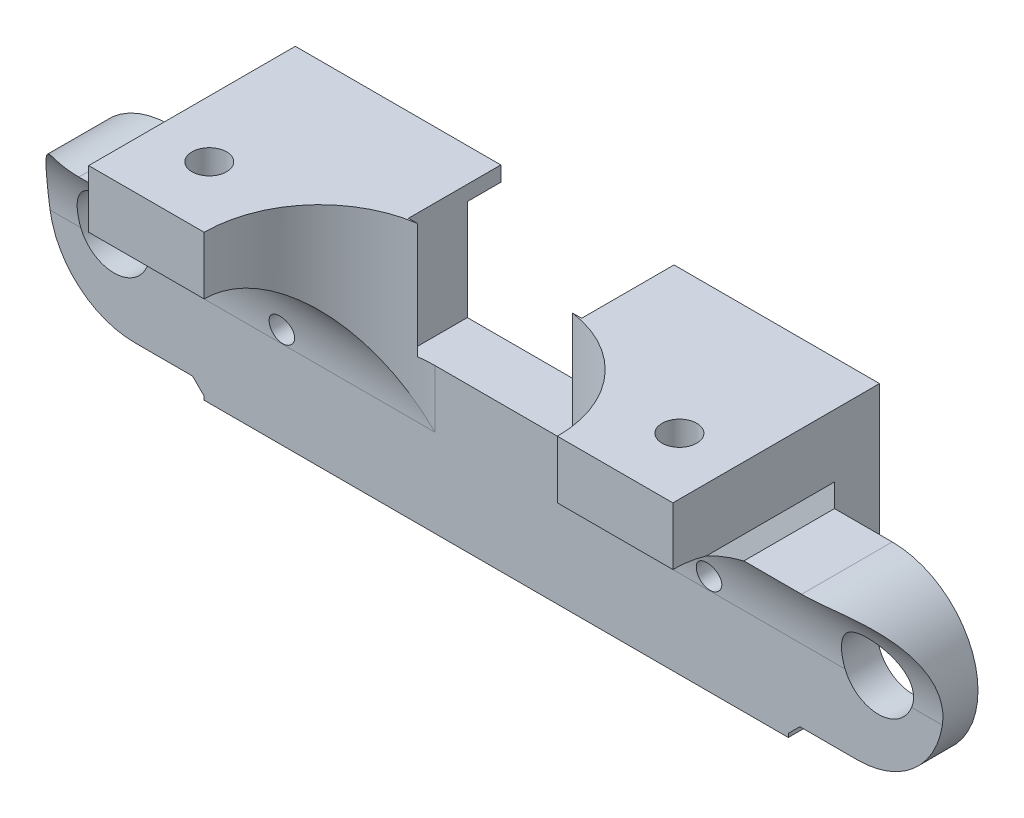
SolidWorks part; units mm, degrees
ref_plane "Front Plane" through (0, 0, 0) normal (0, 0, 1) x (1, 0, 0)
ref_plane "Top Plane" through (0, 0, 0) normal (0, 1, 0) x (1, 0, 0)
ref_plane "Right Plane" through (0, 0, 0) normal (1, 0, 0) x (0, 0, -1)
sketch "Sketch1" plane through (0, 0, 0) normal (0, 0, 1) x (1, 0, 0)
  line L12 (24, 12.55) -> (6.08, 12.55)
  line L13 (6.08, 12.55) -> (-6.08, 12.55)
  line L14 (-6.08, 12.55) -> (-24, 12.55)
  line L15 (-24, 12.55) -> (-24, -7.45)
  line L16 (-24, -7.45) -> (24, -7.45)
  line L17 (24, -7.45) -> (24, 12.55)
  line L18 (24, 12.55) -> (6.08, 12.55)
  line L19 (6.08, 12.55) -> (-6.08, 12.55)
  line L20 (-6.08, 12.55) -> (-24, 12.55)
  line L21 (-24, 12.55) -> (-24, -7.45)
  line L22 (-24, -7.45) -> (24, -7.45)
  line L23 (24, -7.45) -> (24, 12.55)
  dimension "D1" = 0
extrude "Boss-Extrude1" add sketch "Sketch1" along normal blind 5
sketch "Sketch2" plane through (0, 0, 5) normal (0, 0, 1) x (1, 0, 0)
  line L4 (25.3, -8.75) -> (25.3, 13.85)
  line L5 (25.3, 13.85) -> (-25.3, 13.85)
  line L6 (-25.3, 13.85) -> (-25.3, -8.75)
  line L7 (-25.3, -8.75) -> (25.3, -8.75)
  line L8 (24, -7.45) -> (24, 12.55)
  line L9 (24, 12.55) -> (-24, 12.55)
  line L10 (-24, 12.55) -> (-24, -7.45)
  line L11 (-24, -7.45) -> (24, -7.45)
  line L12 (24, -7.45) -> (24, 12.55)
  line L13 (24, 12.55) -> (-24, 12.55)
  line L14 (-24, 12.55) -> (-24, -7.45)
  line L15 (-24, -7.45) -> (24, -7.45)
  dimension "D1" = 0
  dimension "D2" = 1.3
extrude "Boss-Extrude2" add sketch "Sketch2" against normal offset from surface (7.9 mm away) 0.1
sketch "Sketch3" plane through (0, 0, 0) normal (0, 0, -1) x (-1, 0, 0)
  circle A0 centre (-18.5, 0) radius 1.1
  circle A1 centre (18.5, 0) radius 1.1
  dimension "D1" = 2.2
  dimension "D2" = 2.2
extrude "Cut-Extrude1" cut sketch "Sketch3" along normal through all both and the other way through all
sketch "Sketch4" plane through (0, 0, 5) normal (0, 0, 1) x (1, 0, 0)
  line L0 (25.3, -7.4396) -> (31.3, -7.4396)
  line L1 (25.3, 13.85) -> (25.3, -8.75) construction
  line L2 (0, -1008.75) -> (0, 48991.25) construction
  line L3 (31.3, 7.4204) -> (25.3, 7.4204)
  line L4 (25.3, 7.4204) -> (25.3, -7.4396)
  line L5 (25.3, -8.75) -> (-25.3, -8.75) construction
  line L6 (-25.3, -7.4396) -> (-31.3, -7.4396)
  line L7 (-25.3, 7.4204) -> (-25.3, -7.4396)
  line L8 (-31.3, 7.4204) -> (-25.3, 7.4204)
  arc A0 (31.3, -7.4396) -> (31.3, 7.4204) centre (31.3, -0.0096) ccw
  arc A1 (-31.3, -7.4396) -> (-31.3, 7.4204) centre (-31.3, -0.0096) cw
  point P15 (0, -8.75)
  dimension "D1" = 6
  dimension "D2" = 1.3104
  dimension "D3" = 14.86
extrude "Boss-Extrude3" add sketch "Sketch4" against normal blind 3
chamfer "Chamfer1" distance 1 angle 45 6 edges at (25.3, 7.4204, 3.5) (25.3, -0.0096, 2) (25.3, -7.4396, 3.5) (-25.3, 7.4204, 3.5) (-25.3, -0.0096, 2) (-25.3, -7.4396, 3.5)
sketch "Sketch5" plane through (0, 0, 2) normal (0, 0, -1) x (-1, 0, 0)
  line L0 (-968.7, -0.0096) -> (49031.3, -0.0096) construction
  line L2 (0, -1008.75) -> (0, 48991.25) construction
  line L3 (-25.3, -8.75) -> (25.3, -8.75) construction
  circle A2 centre (-33.1, -0.0096) radius 3.1
  circle A3 centre (33.1, -0.0096) radius 3.1
  point P0 (31.3, -0.0096)
  point P15 (0, -8.75)
  dimension "D1" = 6.2
  dimension "D2" = 1.8
extrude "Cut-Extrude2" cut sketch "Sketch5" against normal blind 3
sketch "Sketch6" plane through (0, 0, 5) normal (0, 0, 1) x (1, 0, 0)
  line L0 (25.3, 13.85) -> (-25.3, 13.85) construction
  line L1 (-25.3, 13.85) -> (-15.3, 13.85)
  line L2 (-25.3, 13.85) -> (-25.3, 8.85)
  line L3 (-25.3, 8.85) -> (-15.3, 8.85)
  line L4 (-15.3, 13.85) -> (-15.3, 8.85)
  line L5 (-25.3, 13.85) -> (-25.3, 8.4204) construction
  line L6 (0, 21.1699) -> (0, -25.8518) construction
  line L7 (25.3, 8.85) -> (15.3, 8.85)
  line L8 (15.3, 13.85) -> (15.3, 8.85)
  line L9 (25.3, 13.85) -> (15.3, 13.85)
  line L10 (25.3, 13.85) -> (25.3, 8.85)
  dimension "D1" = 5
  dimension "D2" = 10
extrude "Boss-Extrude4" add sketch "Sketch6" along normal blind 10
fillet "Fillet1" radius 10 4 edges at (15.3, 11.35, 5) (-15.3, 11.35, 5) (-20.3, 8.85, 5) (20.3, 8.85, 5)
sketch "Sketch7" plane through (0, 13.85, 0) normal (0, 1, 0) x (1, 0, 0)
  line L0 (0, 12.6059) -> (0, -14.8059) construction
  line L1 (-25.3, 2.9) -> (25.3, 2.9) construction
  line L2 (7.5, -5.1) -> (-7.5, -5.1)
  line L3 (7.5, -5.1) -> (7.5, 2.9)
  line L4 (7.5, 2.9) -> (-7.5, 2.9)
  line L5 (-7.5, -5.1) -> (-7.5, 2.9)
  line L6 (7.5, -5.1) -> (-7.5, 2.9) construction
  line L7 (7.5, 2.9) -> (-7.5, -5.1) construction
  point P3 (0, -1.1)
  dimension "D1" = 8
  dimension "D2" = 15
extrude "Cut-Extrude3" cut sketch "Sketch7" against normal blind 10
sketch "Sketch8" plane through (0, 13.85, 0) normal (0, 1, 0) x (1, 0, 0)
  line L0 (0, -14.5347) -> (0, 26.1086) construction
  line L1 (15.4204, -15) -> (25.3, -3.9831)
  line L2 (25.3, -15) -> (0, -15)
  line L3 (25.3, -15) -> (25.3, -3.9831)
  line L4 (25.3, -3.9831) -> (0, -3.9831)
  line L5 (0, -15) -> (0, -3.9831)
  line L6 (25.3, -15) -> (15.4204, -15)
  line L7 (25.3, -15) -> (25.3, -3.9831)
  line L8 (25.3, -3.9831) -> (15.4204, -3.9831)
  line L9 (15.4204, -15) -> (15.4204, -3.9831)
  line L10 (25.3, -15) -> (15.4204, -3.9831)
  circle A0 centre (20.3602, -9.4915) radius 1.5
  circle A1 centre (-20.3602, -9.4915) radius 1.5
extrude "Cut-Extrude4" cut sketch "Sketch8" against normal up to next contours A1 | A0
sketch "Sketch10" plane through (0, 0, 0) normal (0, 0, -1) x (-1, 0, 0)
  line L0 (-38.73, -0.0096) -> (38.73, -0.0096)
  line L1 (-16.4, 13.85) -> (-16.4, -8.75)
  line L2 (-7.5, 13.85) -> (-25.3, 13.85) construction
  line L3 (-25.3, -8.75) -> (25.3, -8.75) construction
  arc A0 (-31.3, 7.4204) -> (-31.3, -7.4396) centre (-31.3, -0.0096) ccw construction
  arc A1 (31.3, -7.4396) -> (31.3, 7.4204) centre (31.3, -0.0096) ccw construction
sketch "Sketch11" plane through (0, 13.85, 0) normal (0, 1, 0) x (1, 0, 0)
  line L0 (20.3, -15) -> (20.3, 2.9)
  line L1 (25.3, -15) -> (15.3, -15) construction
  line L2 (7.5, 2.9) -> (25.3, 2.9) construction
